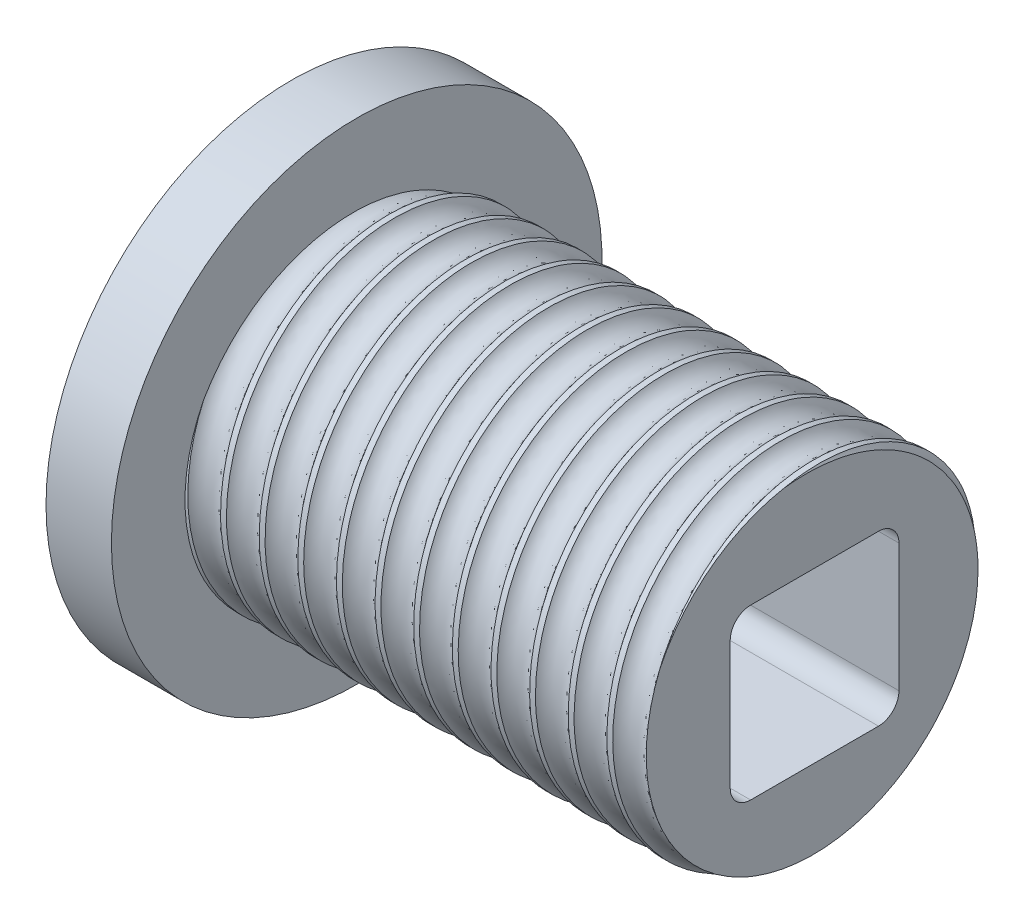
SolidWorks part; units mm, degrees
ref_plane "Front Plane" through (0, 0, 0) normal (0, 0, 1) x (1, 0, 0)
ref_plane "Top Plane" through (0, 0, 0) normal (0, 1, 0) x (1, 0, 0)
ref_plane "Right Plane" through (0, 0, 0) normal (1, 0, 0) x (0, 0, -1)
sketch "Sketch1" plane through (0, 0, 0) normal (1, 0, 0) x (0, 0, -1)
  circle A0 centre (0, 0) radius 6.6675
  dimension "D1" = 13.335
extrude "Boss-Extrude1" add sketch "Sketch1" along normal blind 17.78
sketch "Sketch2" plane through (0, 0, 0) normal (-1, 0, 0) x (0, 0, 1)
  circle A0 centre (0, 0) radius 6.6675 construction
  circle A1 centre (0, 0) radius 6.6675
curve "Helix/Spiral1" pitch 1.5 height 19.05 radius 6.6675 centre (0, 0, 0) axis (1, 0, 0) start towards (0, 0, -1)
ref_plane "Plane1" through (0, 0, -6.6675) normal (0.0358, 0.9994, 0) x (0.9994, -0.0358, 0)
sketch "Sketch3" plane through (0, 0, -0.3175) normal (-0.0358, -0.9994, 0) x (-0.9994, 0.0358, 0)
  line L0 (0, 6.35) -> (-17.7686, 6.35) construction
  line L1 (-0.6364, 6.35) -> (0.6364, 6.35)
  arc A1 (-0.6364, 6.35) -> (0.6364, 6.35) centre (0, 6.7469) ccw
  dimension "D1" = 1.5
  dimension "D2" = 0.3969
sweep "Cut-Sweep3" cut profiles "Sketch3" path "Helix/Spiral1" align with end faces yes
sketch "Sketch5" plane through (0, 0, 0) normal (-1, 0, 0) x (0, 0, 1)
  circle A0 centre (0, 0) radius 9.525
  dimension "D1" = 19.05
extrude "Boss-Extrude2" add sketch "Sketch5" along normal blind 2.54
sketch "Sketch6" plane through (-2.54, 0, 0) normal (-1, 0, 0) x (0, 0, 1)
  line L1 (-3.2766, -3.2766) -> (3.2766, -3.2766)
  line L2 (-3.2766, -3.2766) -> (-3.2766, 3.2766)
  line L3 (-3.2766, 3.2766) -> (3.2766, 3.2766)
  line L4 (3.2766, -3.2766) -> (3.2766, 3.2766)
  line L5 (-3.2766, -3.2766) -> (3.2766, 3.2766) construction
  line L6 (-3.2766, 3.2766) -> (3.2766, -3.2766) construction
  point P0 (0, 0)
  dimension "D1" = 6.5532
extrude "Cut-Extrude1" cut sketch "Sketch6" against normal through all
fillet "Fillet1" radius 0.7937 4 edges at (7.62, -3.2766, 3.2766) (7.62, -3.2766, -3.2766) (7.62, 3.2766, -3.2766) (7.62, 3.2766, 3.2766)
